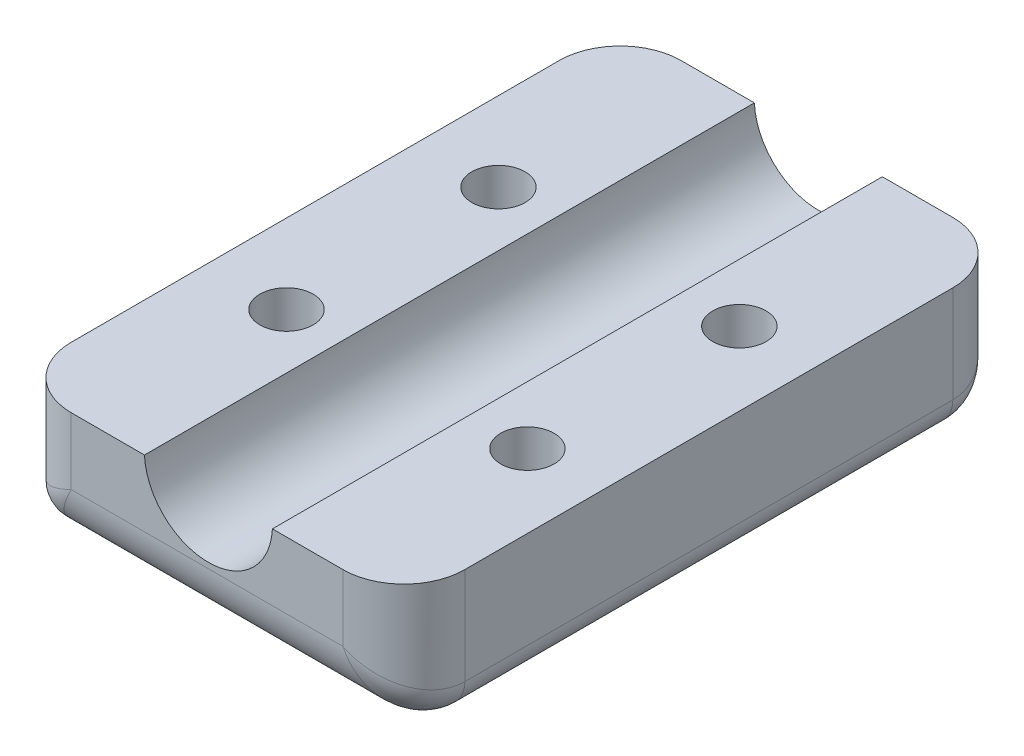
SolidWorks part; units mm, degrees
ref_plane "Front Plane" through (0, 0, 0) normal (0, 0, 1) x (1, 0, 0)
ref_plane "Top Plane" through (0, 0, 0) normal (0, 1, 0) x (1, 0, 0)
ref_plane "Right Plane" through (0, 0, 0) normal (1, 0, 0) x (0, 0, -1)
sketch "Sketch1" plane through (0, 0, 0) normal (0, 0, 1) x (1, 0, 0)
  line L0 (4.1954, -7.1974) -> (12.8176, -7.1974)
  line L1 (-13, -7.1974) -> (-4.1954, -7.1974)
  line L2 (-13, -7.1974) -> (-13, -13.5614)
  line L3 (-11, -15.5614) -> (10.8176, -15.5614)
  line L4 (12.8176, -7.1974) -> (12.8176, -13.5614)
  arc A0 (-4.1954, -7.1974) -> (4.1954, -7.1974) centre (0, -7) ccw
  arc A1 (10.8176, -15.5614) -> (12.8176, -13.5614) centre (10.8176, -13.5614) ccw
  arc A2 (-13, -13.5614) -> (-11, -15.5614) centre (-11, -13.5614) ccw
  dimension "D1" = 2
extrude "Boss-Extrude1" add sketch "Sketch1" against normal blind 40
sketch "Sketch2" plane through (0, -15.5614, 0) normal (0, -1, 0) x (1, 0, 0)
  circle A0 centre (-7.8, -12.9205) radius 1.75 construction
  circle A1 centre (-7.8, -26.8205) radius 1.75 construction
  circle A2 centre (8, -12.9205) radius 1.75 construction
  circle A3 centre (8, -26.8205) radius 1.75 construction
  circle A4 centre (-7.8, -12.9205) radius 1.75
  circle A5 centre (-7.8, -26.8205) radius 1.75
  circle A6 centre (8, -12.9205) radius 1.75
  circle A7 centre (8, -26.8205) radius 1.75
extrude "Cut-Extrude1" cut sketch "Sketch2" against normal blind 20
fillet "Fillet1" radius 4 10 edges at (-12.4142, -14.9756, 0) (-0.0912, -15.5614, 0) (12.2318, -14.9756, 0) (-12.4142, -14.9756, -40) (-0.0912, -15.5614, -40) (12.2318, -14.9756, -40) (-13, -10.3794, 0) (12.8176, -10.3794, 0) (-13, -10.3794, -40) (12.8176, -10.3794, -40)
sketch "Sketch3" plane through (0, -15.5614, 0) normal (0, -1, 0) x (1, 0, 0)
  circle A0 centre (-7.8, -12.9205) radius 3.5
  circle A1 centre (8, -12.9205) radius 3.5
  circle A2 centre (-7.8, -26.8205) radius 3.5
  circle A3 centre (8, -26.8205) radius 3.5
  dimension "D1" = 7
  dimension "D2" = 7
  dimension "D3" = 7
  dimension "D4" = 7
extrude "Cut-Extrude2" cut sketch "Sketch3" against normal blind 3
